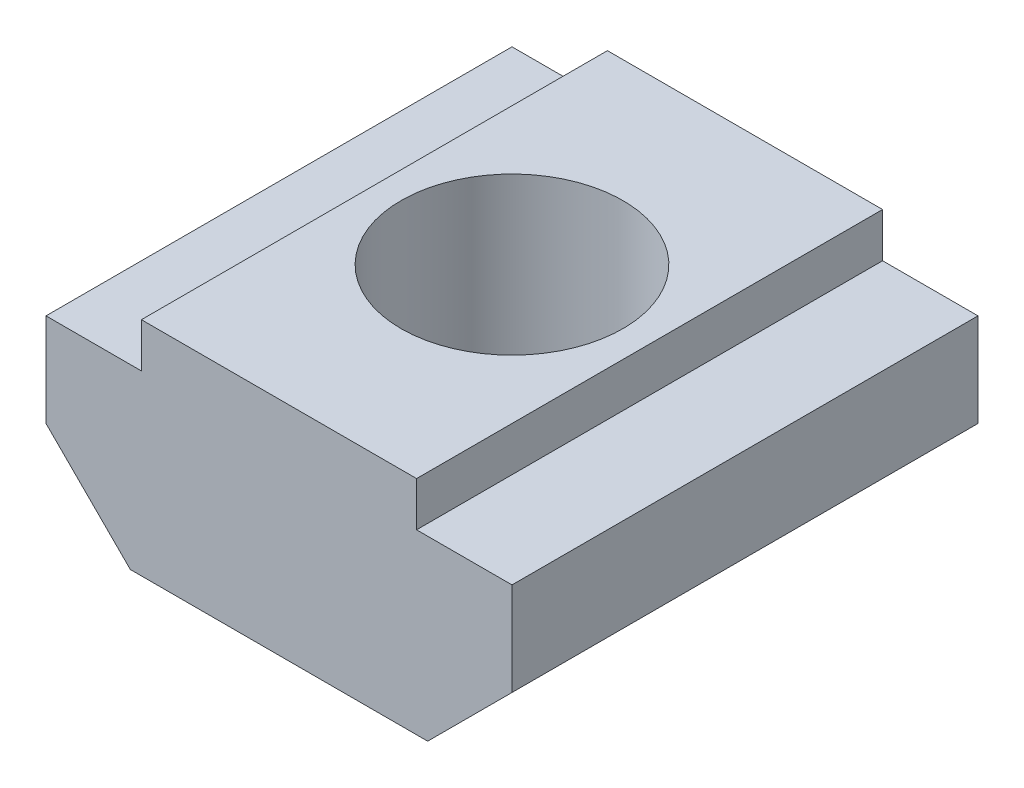
SolidWorks part; units mm, degrees
ref_plane "Front Plane" through (0, 0, 0) normal (0, 0, 1) x (1, 0, 0)
ref_plane "Top Plane" through (0, 0, 0) normal (0, 1, 0) x (1, 0, 0)
ref_plane "Right Plane" through (0, 0, 0) normal (1, 0, 0) x (0, 0, -1)
sketch "Sketch2" plane through (0, 0, 0) normal (0, 0, 1) x (1, 0, 0)
  line L0 (-5.25, 1.5) -> (5.25, 1.5)
  line L1 (-5.25, -2.5) -> (5.25, -2.5)
  line L2 (-5.25, -2.5) -> (-5.25, 2.5)
  line L3 (-5.25, 2.5) -> (5.25, 2.5)
  line L4 (5.25, -2.5) -> (5.25, 2.5)
  line L5 (-5.25, -2.5) -> (5.25, 2.5) construction
  line L6 (-5.25, 2.5) -> (5.25, -2.5) construction
  line L7 (-3.1, 2.5) -> (3.1, 2.5)
  line L8 (-3.1, 2.5) -> (-3.1, 1.5)
  line L9 (-3.1, 1.5) -> (3.1, 1.5)
  line L10 (3.1, 2.5) -> (3.1, 1.5)
  line L11 (-3.35, -2.5) -> (-5.25, -0.6)
  line L12 (5.25, -0.6) -> (3.35, -2.5)
  point P0 (0, 0)
  point P10 (0, 1.5)
  dimension "D1" = 10.5
  dimension "D2" = 5
  dimension "D3" = 1
  dimension "D4" = 6.2
  dimension "D5" = 3.35
  dimension "D6" = 45
  dimension "D7" = 45
extrude "Boss-Extrude1" add sketch "Sketch2" along normal blind 10.5 contours L12 L4 L0 L2 L11 L1 | L10 L3 L8 L0 region at (0, -0.3715, 0) region at (0, 2, 0)
sketch "Sketch3" plane through (0, 2.5, 0) normal (0, 1, 0) x (1, 0, 0)
  line L0 (-3.1, 0) -> (3.1, -10.5) construction
  line L4 (3.1, 0) -> (-3.1, 0)
  line L5 (-3.1, 0) -> (-3.1, -10.5)
  line L6 (-3.1, -10.5) -> (3.1, -10.5)
  line L7 (3.1, -10.5) -> (3.1, 0)
  line L8 (3.1, 0) -> (-3.1, 0)
  line L9 (-3.1, 0) -> (-3.1, -10.5)
  line L10 (-3.1, -10.5) -> (3.1, -10.5)
  line L11 (3.1, -10.5) -> (3.1, 0)
  circle A0 centre (0, -5.25) radius 2.5
  dimension "D2" = 5
  dimension "D1" = 0
extrude "Cut-Extrude1" cut sketch "Sketch3" against normal through all contours L0 A0 | A0 L0 region at (0.9136, 2.5, 4.7105) region at (-0.9136, 2.5, 5.7895)
